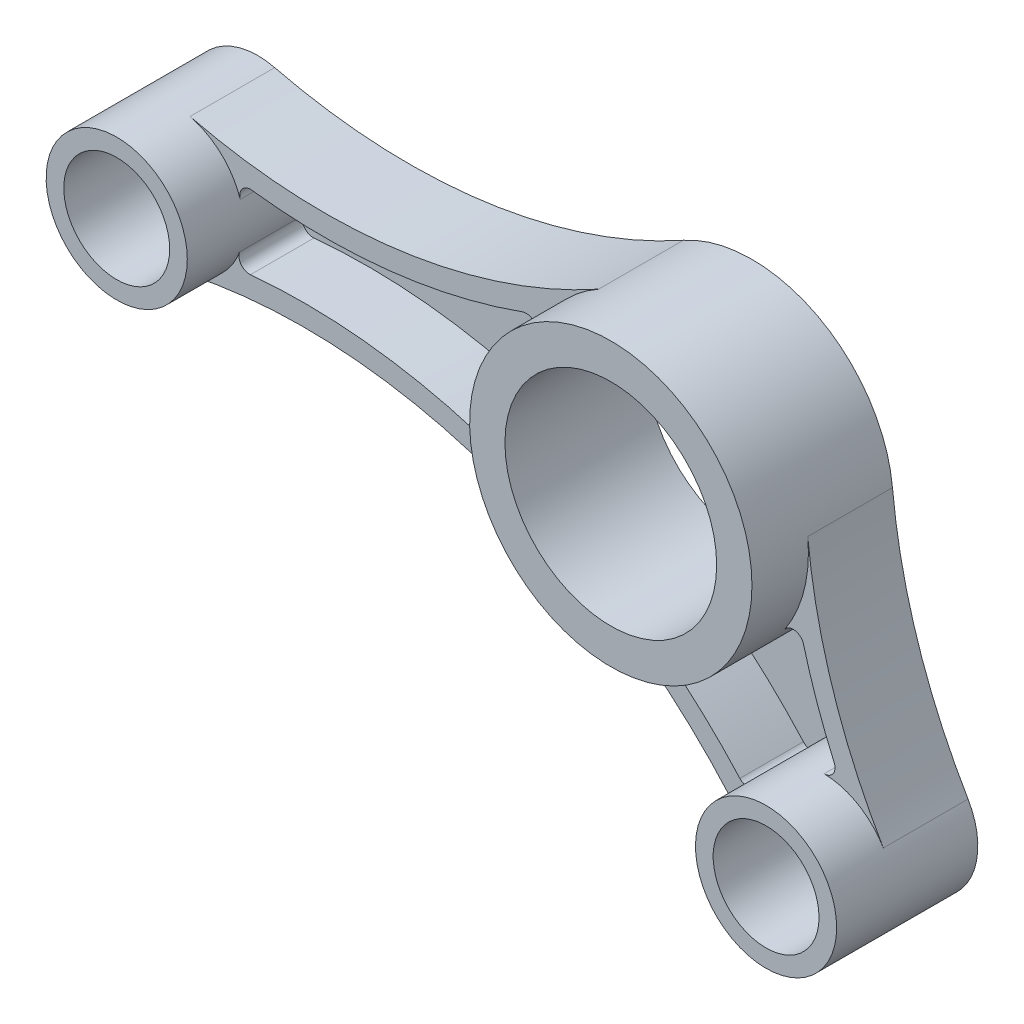
SolidWorks part; units mm, degrees
ref_plane "Front Plane" through (0, 0, 0) normal (0, 0, 1) x (1, 0, 0)
ref_plane "Top Plane" through (0, 0, 0) normal (0, 1, 0) x (1, 0, 0)
ref_plane "Right Plane" through (0, 0, 0) normal (1, 0, 0) x (0, 0, -1)
sketch "Sketch1" plane through (0, 0, 0) normal (0, 0, 1) x (1, 0, 0)
  line L0 (-1307.1445, 0) -> (64050.0802, 0) construction
  line L2 (0, -1307.1445) -> (0, 64050.0802) construction
  line L4 (0, 0) -> (22, -36) construction
  line L5 (0, 0) -> (0.3463, 0) construction
  circle A0 centre (-70, 0) radius 10
  circle A1 centre (-70, 0) radius 7.5
  circle A2 centre (0, 0) radius 20
  circle A4 centre (22, -36) radius 7.5
  circle A5 centre (22, -36) radius 10
  arc A6 (13.8428, -41.7845) -> (-67.935, -9.7845) centre (-51.4148, -88.0602) ccw
  arc A7 (-67.619, 9.7124) -> (-9.7143, 17.4824) centre (-48.5714, 87.4118) ccw
  arc A8 (19.9055, 1.9422) -> (30.6142, -30.921) centre (99.5274, 9.7112) ccw
  arc A9 (-61.6107, 5.4424) -> (-16.9028, 10.6908) centre (-48.5714, 87.4118) ccw
  arc A10 (12.0952, -34.6235) -> (-4.7336, -19.4318) centre (-51.4148, -88.0602) ccw
  arc A11 (18.4026, -7.8323) -> (24.7937, -26.3982) centre (99.5274, 9.7112) ccw
  arc A12 (-14.5955, -13.6738) -> (-61.7914, -5.7114) centre (-51.4148, -88.0602) ccw
  arc A13 (-68.3333, 6.7987) -> (-8.2571, 14.86) centre (-48.5714, 87.4118) ccw construction
  arc A14 (16.29, -40.0491) -> (-68.5545, -6.8491) centre (-51.4148, -88.0602) ccw construction
  circle A15 centre (0, 0) radius 15
  arc A16 (16.9196, 1.6509) -> (28.0299, -32.4447) centre (99.5274, 9.7112) ccw construction
  dimension "D1" = 40
  dimension "D2" = 30
  dimension "D3" = 20
  dimension "D4" = 15
  dimension "D7" = 22
  dimension "D9" = 15
  dimension "D10" = 20
  dimension "D11" = 160
  dimension "D12" = 160
  dimension "D13" = 160
  dimension "D5" = 70
  dimension "D6" = 22
  dimension "D8" = 36
  dimension "D14" = 3
extrude "Boss-Extrude4" add sketch "Sketch1" along normal blind 20 contours A2
extrude "Boss-Extrude5" add sketch "Sketch1<10>" along normal blind 20 contours A0 A1 | A5 A4 | A15 region at (-60.7282, -2.9082, 0) region at (12.5599, -38.3038, 0)
sketch "Sketch1<10>" plane through (0, 0, 0) normal (0, 0, 1) x (1, 0, 0) same geometry as "Sketch1"
extrude "Cut-Extrude1" cut sketch "Sketch1<11>" along normal blind 20 contours A15
sketch "Sketch1<11>" plane through (0, 0, 0) normal (0, 0, 1) x (1, 0, 0) same geometry as "Sketch1"
extrude "Boss-Extrude6" add sketch "Sketch1<12>" along normal blind 12 contours A0 A9 A2 A7 | A2 A12 A0 A6 A5 A10 | A2 A11 A5 A8 region at (-38.7494, 7.85, 0) region at (-37.7562, -7.1007, 0) region at (22.7213, -16.1899, 0)
sketch "Sketch1<12>" plane through (0, 0, 0) normal (0, 0, 1) x (1, 0, 0) same geometry as "Sketch1"
extrude "Boss-Extrude7" add sketch "Sketch1<13>" along normal blind 3 contours A12 A2 A9 A0 | A11 A2 A10 A5 region at (-36.6976, -0.6859, 0) region at (12.6273, -22.1299, 0)
sketch "Sketch1<13>" plane through (0, 0, 0) normal (0, 0, 1) x (1, 0, 0) same geometry as "Sketch1"
fillet "Fillet1" radius 1.5 8 edges at (12.0952, -34.6235, 7.5) (24.7937, -26.3982, 7.5) (-4.7336, -19.4318, 7.5) (18.4026, -7.8323, 7.5) (-14.5955, -13.6738, 7.5) (-16.9028, 10.6908, 7.5) (-61.7914, -5.7114, 7.5) (-61.6107, 5.4424, 7.5)
